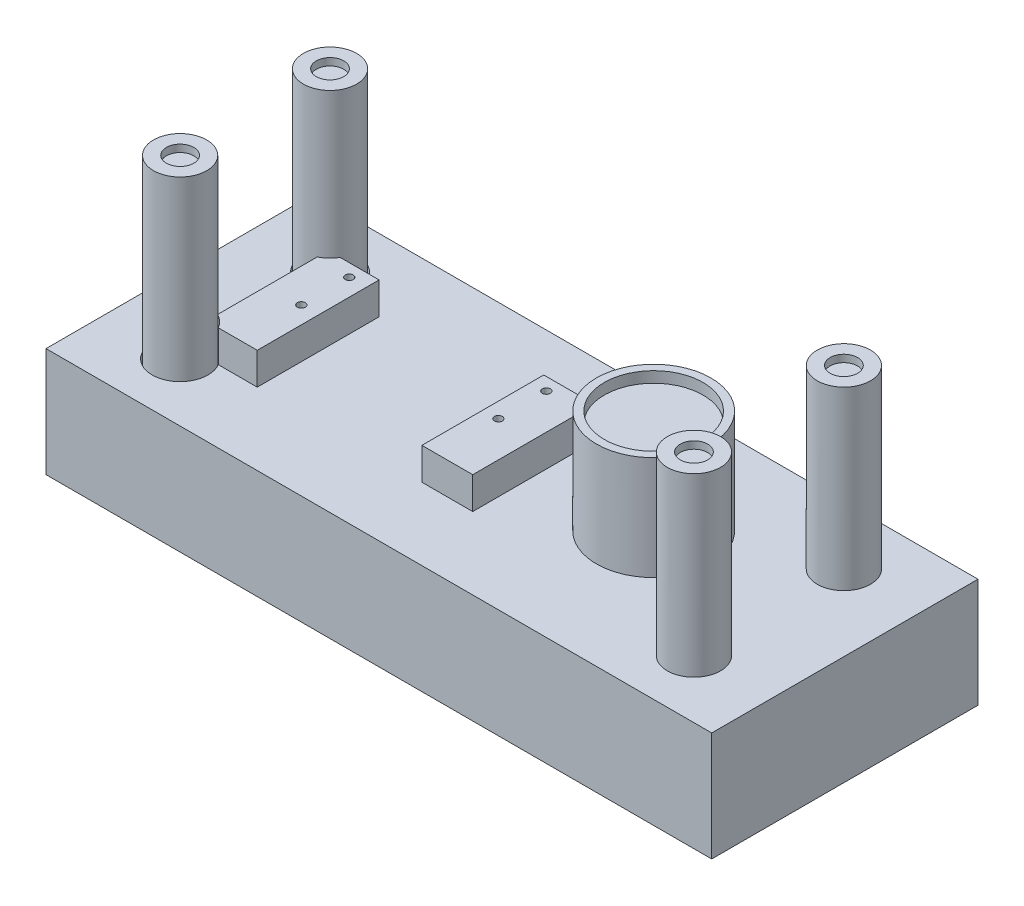
SolidWorks part; units mm, degrees
ref_plane "Front Plane" through (0, 0, 0) normal (0, 0, 1) x (1, 0, 0)
ref_plane "Top Plane" through (0, 0, 0) normal (0, 1, 0) x (1, 0, 0)
ref_plane "Right Plane" through (0, 0, 0) normal (1, 0, 0) x (0, 0, -1)
sketch "Sketch1" plane through (0, 0, 0) normal (0, 1, 0) x (1, 0, 0)
  line L1 (-125, -50) -> (125, -50)
  line L2 (-125, -50) -> (-125, 50)
  line L3 (-125, 50) -> (125, 50)
  line L4 (125, -50) -> (125, 50)
  line L5 (0, 50) -> (0, -50) construction
  line L6 (-125, 0) -> (125, 0) construction
  line L7 (-87.9863, 22.88) -> (-72.79, 22.88)
  line L8 (-91.88, 19.2734) -> (-91.88, -19.2734)
  line L9 (-87.9863, -22.88) -> (-72.79, -22.88)
  line L10 (-72.79, 22.88) -> (-72.79, -22.88)
  line L11 (-10.96, 22.88) -> (8.13, 22.88)
  line L12 (-10.96, 22.88) -> (-10.96, -22.88)
  line L13 (-10.96, -22.88) -> (8.13, -22.88)
  line L14 (8.13, 22.88) -> (8.13, -22.88)
  circle A0 centre (-96.485, 28.15) radius 10
  circle A1 centre (-96.485, -28.15) radius 10
  circle A2 centre (96.485, 28.15) radius 10
  circle A3 centre (96.485, -28.15) radius 10
  circle A4 centre (48.387, 4.8142) radius 21.5
  circle A5 centre (48.387, 4.8142) radius 18.55
  circle A6 centre (-96.485, 28.15) radius 5.15
  circle A7 centre (-96.485, -28.15) radius 5.15
  circle A8 centre (96.485, 28.15) radius 5.15
  circle A9 centre (96.485, -28.15) radius 5.15
  circle A10 centre (-96.485, 28.15) radius 10.5
  circle A11 centre (-96.485, -28.15) radius 10.5
  circle A12 centre (96.485, 28.15) radius 10.5
  circle A13 centre (96.485, -28.15) radius 10.5
  point P0 (0, 0)
  dimension "D3" = 20
  dimension "D6" = 53.46
  dimension "D8" = 43
  dimension "D9" = 37.1
  dimension "D15" = 10.3
  dimension "D16" = 21
  dimension "D1" = 250
  dimension "D2" = 100
  dimension "D4" = 192.97
  dimension "D5" = 56.3
  dimension "D7" = 58.31
  dimension "D10" = 19.09
  dimension "D11" = 45.76
  dimension "D12" = 33.12
  dimension "D13" = 114.04
  dimension "D14" = 19.09
extrude "Boss-Extrude1" add sketch "Sketch1" against normal blind 41 contours L1 L4 L3 L2
extrude "Boss-Extrude2" add sketch "Sketch1<4>" along normal blind 12 contours A1 L9 L10 L7 A0 L8 | L14 L11 L12 L13 region at (-82.1271, 0, 0) region at (-1.415, 0, 0)
sketch "Sketch1<4>" plane through (0, 0, 0) normal (0, 1, 0) x (1, 0, 0) same geometry as "Sketch1"
extrude "Boss-Extrude3" add sketch "Sketch1<5>" along normal blind 39 contours A4 A5 region at (27.4951, 0, -4.8142)
sketch "Sketch1<5>" plane through (0, 0, 0) normal (0, 1, 0) x (1, 0, 0) same geometry as "Sketch1"
extrude "Boss-Extrude4" add sketch "Sketch1<6>" along normal blind 34.9 contours A5
sketch "Sketch1<6>" plane through (0, 0, 0) normal (0, 1, 0) x (1, 0, 0) same geometry as "Sketch1"
extrude "Cut-Extrude1" cut sketch "Sketch1<9>" against normal blind 5 contours L8 A11 L9 A1 | A1 A7 | A7 | L7 A10 L8 A0 | A0 A6 | A6 | L9 A11 L8 A1 | L8 A10 L7 A0 region at (-86.582, 0, -25.3288) region at (-89.5989, 0, -20.7343) region at (-89.8817, 0, -21.0212) region at (-89.5989, 0, 20.7343) region at (-92.177, 0, 18.9935) region at (-89.8817, 0, 21.0212) region at (-96.485, 0, -28.15) region at (-96.485, 0, 28.15)
sketch "Sketch1<9>" plane through (0, 0, 0) normal (0, 1, 0) x (1, 0, 0) same geometry as "Sketch1"
extrude "Boss-Extrude7" add sketch "Sketch1<10>" along normal blind 66.2 contours A3 A9 | A9 | A2 A8 | A8 | A3 region at (86.7678, 0, -28.15) region at (86.7678, 0, 28.15) region at (96.485, 0, -28.15) region at (96.485, 0, 28.15)
sketch "Sketch1<10>" plane through (0, 0, 0) normal (0, 1, 0) x (1, 0, 0) same geometry as "Sketch1"
extrude "Boss-Extrude8" add sketch "Sketch1<11>" along normal blind 66.2 and the other way up to surface (5 mm away) separate body contours A1 A7 | A7 | A6 | A0 A6 region at (-89.8817, 0, -21.0212) region at (-89.8817, 0, 21.0212) region at (-96.485, 0, -28.15) region at (-96.485, 0, 28.15) other way up to face at (-96.485, -5, 38.65)
sketch "Sketch1<11>" plane through (0, 0, 0) normal (0, 1, 0) x (1, 0, 0) same geometry as "Sketch1"
extrude "Cut-Extrude2" cut sketch "Sketch1<12>" against normal blind 2.75 from surface contours A7 | A6 | A9 | A8 starting at face at (96.485, 66.2, 38.15)
sketch "Sketch1<12>" plane through (0, 0, 0) normal (0, 1, 0) x (1, 0, 0) same geometry as "Sketch1"
sketch "Sketch3" plane through (0, 12, 0) normal (0, 1, 0) x (1, 0, 0)
  circle A0 centre (-79.2548, 18.1338) radius 1.5
  circle A1 centre (-79.2548, 0.1338) radius 1.5
  circle A2 centre (-5.2548, 18.1338) radius 1.5
  circle A3 centre (-5.2548, 0.1338) radius 1.5
  point P8 (0, 0)
  point P9 (0, 0)
  point P10 (0, 0)
  point P11 (0, 0)
  dimension "D1" = 3
  dimension "D2" = 18
  dimension "D3" = 74
  dimension "D4" = 8.02
  dimension "D5" = 19.93
extrude "Cut-Extrude3" cut sketch "Sketch3" against normal blind 12
sketch "Sketch4" plane through (0, -41, 0) normal (0, -1, 0) x (1, 0, 0)
  line L0 (-125, -50) -> (125, -50) construction
  line L1 (-105, 19.5) -> (45, 19.5)
  line L2 (-105, 19.5) -> (-105, -30)
  line L3 (-105, -30) -> (45, -30)
  line L4 (45, 19.5) -> (45, -30)
  line L5 (-125, 50) -> (-125, -50) construction
  dimension "D1" = 150
  dimension "D2" = 49.5
  dimension "D3" = 20
  dimension "D4" = 20
extrude "Cut-Extrude4" cut sketch "Sketch4" against normal blind 31 contours L1 L4 L3 L2
